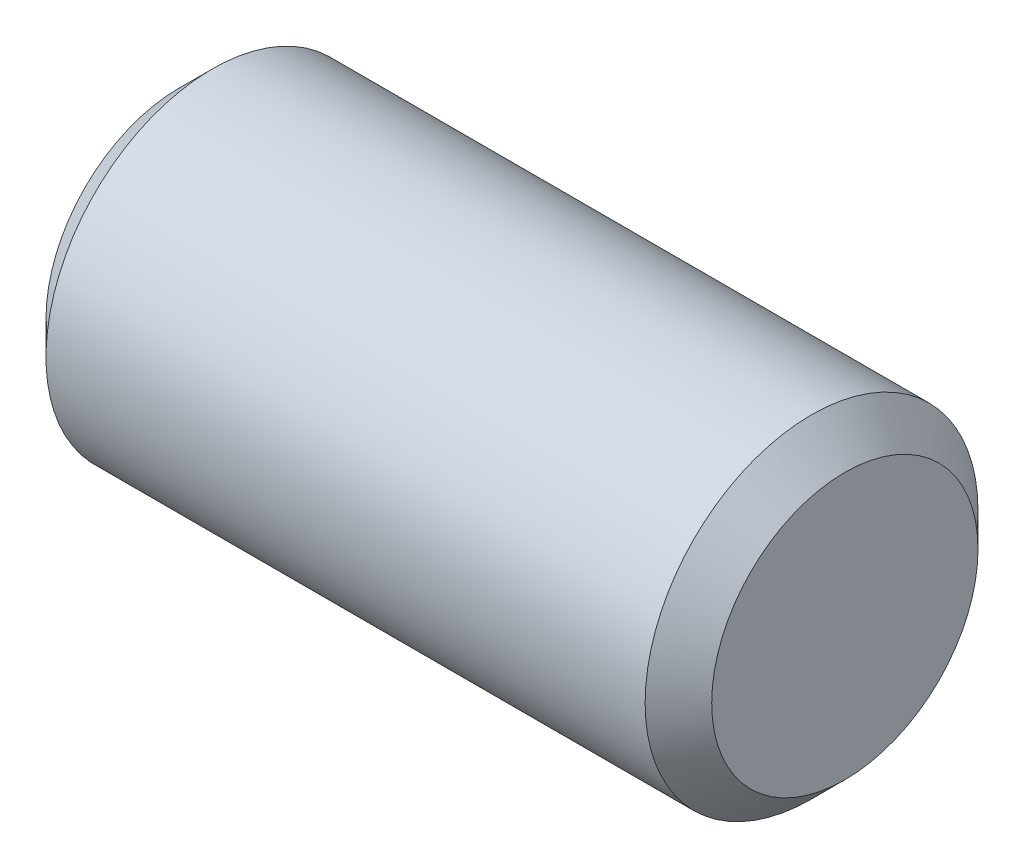
SolidWorks part; units mm, degrees
ref_plane "Front" through (0, 0, 0) normal (0, 0, 1) x (1, 0, 0)
ref_plane "Top" through (0, 0, 0) normal (0, 1, 0) x (1, 0, 0)
ref_plane "Right" through (0, 0, 0) normal (1, 0, 0) x (0, 0, -1)
sketch "Sketch1" plane through (0, 0, 0) normal (0, 0, 1) x (1, 0, 0)
  line L0 (-4.7625, 0) -> (4.7625, 0) construction
  line L1 (4.7625, 2.3813) -> (4.7625, -2.3813) construction
  line L2 (-4.7625, 2.3813) -> (-4.7625, -2.3813) construction
  dimension "Length" = 9.525
  dimension "Diameter" = 4.7625
sketch "Sketch2" plane through (0, 0, 0) normal (1, 0, 0) x (0, 0, -1)
  circle A0 centre (0, 0) radius 2.3813
extrude "Extrude1" add sketch "Sketch2" against normal up to vertex (4.7625 mm away) and the other way up to vertex (4.7625 mm away) up to point (-4.7625, 2.3813, 0) other way up to point (4.7625, 2.3813, 0)
chamfer "Chamfer1" distance 0.4763 angle 45 2 edges at (4.7625, 0, -2.3813) (-4.7625, 0, -2.3813)
equation "\"D1@Chamfer1\" = \"Diameter@Sketch1\"*.1"
